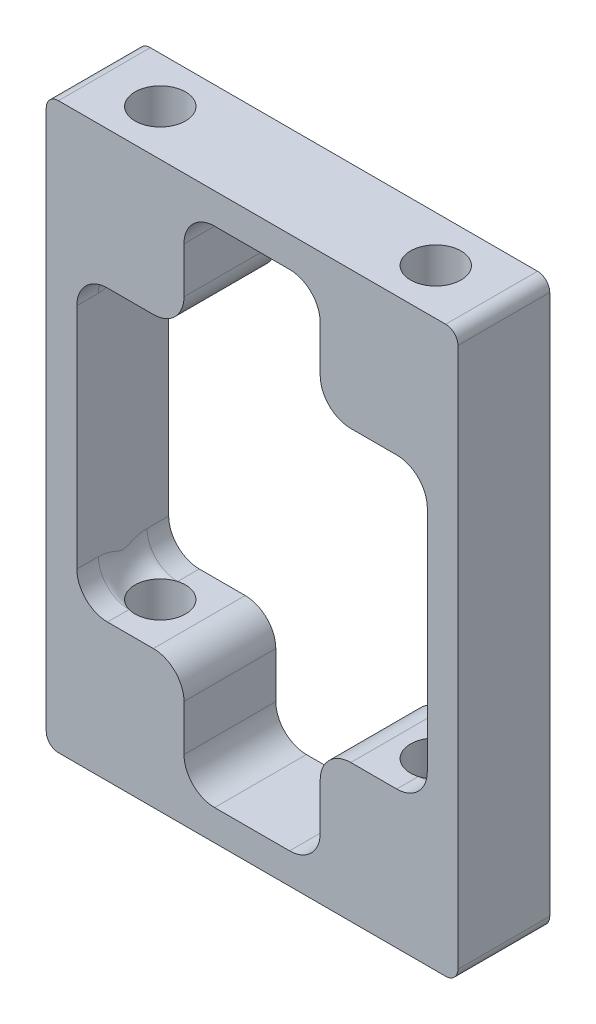
SolidWorks part; units mm, degrees
material "1060 合金"
ref_plane "前视基准面" through (0, 0, 0) normal (0, 0, 1) x (1, 0, 0)
ref_plane "上视基准面" through (0, 0, 0) normal (0, 1, 0) x (1, 0, 0)
ref_plane "右视基准面" through (0, 0, 0) normal (1, 0, 0) x (0, 0, -1)
other "Configuration Table"
sketch "草图1" plane through (0, 0, 0) normal (0, 0, 1) x (1, 0, 0)
  line L1 (-13.45, -18.45) -> (13.45, -18.45)
  line L2 (-13.45, -18.45) -> (-13.45, 18.45)
  line L3 (-13.45, 18.45) -> (13.45, 18.45)
  line L4 (13.45, -18.45) -> (13.45, 18.45)
  line L5 (-13.45, -18.45) -> (13.45, 18.45) construction
  line L6 (-13.45, 18.45) -> (13.45, -18.45) construction
  point P0 (0, 0)
  dimension "D1" = 26.9
  dimension "D2" = 36.9
extrude "凸台-拉伸1" add sketch "草图1" along normal mid plane 6
sketch "草图2" plane through (0, 18.45, 0) normal (0, 1, 0) x (1, 0, 0)
  line L0 (-9, 0) -> (9, 0) construction
  circle A0 centre (-9, 0) radius 1
  circle A1 centre (9, 0) radius 1
  point P4 (0, 0)
  dimension "D2" = 2
  dimension "D1" = 18
extrude "切除-拉伸1" cut sketch "草图2" against normal blind 10
fillet "圆角2" radius 0.8 4 edges at (13.45, -18.45, 0) (-13.45, -18.45, 0) (-13.45, 18.45, 0) (13.45, 18.45, 0)
hole_wizard "M4 螺纹孔1" positions "草图5" profile "草图6" tap size "M4" standard "GB"
sketch "草图5" plane through (0, 18.45, 0) normal (0, 1, 0) x (1, 0, 0)
  point P0 (-9, 0)
  point P3 (9, 0)
sketch "草图6" plane through (-9, 18.45, 0) normal (1, 0, 0) x (0, 0, 1)
  line L0 (0, 0) -> (0, 10.9914)
  line L1 (0, 10.9914) -> (1.65, 10)
  line L2 (1.65, 10) -> (1.65, 0)
  line L5 (1.65, 0) -> (0, 0)
  line L10 (0, 10.9914) -> (-1.65, 10) construction
  line L11 (0, -6.35) -> (0, 107.95) construction
  dimension "螺纹孔钻头直径" = 3.3
  dimension "螺纹孔钻头深度" = 10
  dimension "导头角度" = 118
cosmetic thread "孔螺蚊线1" parameters "D1"=8, "D2"=4
cosmetic thread "孔螺蚊线2" parameters "D1"=8, "D2"=4
mirror "镜向1" about plane through (0, 0, 0) normal (0, 1, 0) of "M4 螺纹孔1"
sketch "草图7" plane through (0, 0, 3) normal (0, 0, 1) x (1, 0, 0)
  line L0 (-4.45, 16.45) -> (4.45, 16.45)
  line L1 (0, 0) -> (50000, 0) construction
  line L2 (-4.45, 16.45) -> (-4.45, 9.45)
  line L3 (-4.45, 9.45) -> (-11.45, 9.45)
  line L4 (-11.45, 9.45) -> (-11.45, -9.45)
  line L5 (4.45, 16.45) -> (4.45, 9.45)
  line L6 (4.45, 9.45) -> (11.45, 9.45)
  line L7 (11.45, 9.45) -> (11.45, -9.45)
  line L8 (0, 0) -> (0, -50000) construction
  line L9 (-13.45, 17.65) -> (-13.45, -17.65) construction
  line L10 (12.65, 18.45) -> (-12.65, 18.45) construction
  line L12 (-11.45, 9.45) -> (-11.45, 0)
  line L13 (-4.45, 9.45) -> (-11.45, 9.45)
  line L14 (-4.45, 16.45) -> (-4.45, 9.45)
  line L15 (11.45, 9.45) -> (11.45, 0)
  line L16 (4.45, 9.45) -> (11.45, 9.45)
  line L17 (4.45, 16.45) -> (4.45, 9.45)
  line L18 (-4.45, 16.45) -> (-4.45, 9.45)
  line L19 (-4.45, 9.45) -> (-11.45, 9.45)
  line L20 (-11.45, 9.45) -> (-11.45, 0)
  line L21 (4.45, 16.45) -> (4.45, 9.45)
  line L22 (4.45, 9.45) -> (11.45, 9.45)
  line L23 (11.45, 9.45) -> (11.45, 0)
  line L24 (-11.45, 9.45) -> (-11.45, 0)
  line L25 (-4.45, 9.45) -> (-11.45, 9.45)
  line L26 (-4.45, 16.45) -> (-4.45, 9.45)
  line L27 (11.45, 9.45) -> (11.45, 0)
  line L28 (4.45, 9.45) -> (11.45, 9.45)
  line L29 (4.45, 16.45) -> (4.45, 9.45)
  line L30 (4.45, -9.45) -> (11.45, -9.45)
  line L31 (4.45, -16.45) -> (4.45, -9.45)
  line L32 (-4.45, -16.45) -> (4.45, -16.45)
  line L33 (-4.45, -16.45) -> (-4.45, -9.45)
  line L34 (-4.45, -9.45) -> (-11.45, -9.45)
  dimension "D1" = 2
  dimension "D2" = 9
  dimension "D3" = 9
  dimension "D4" = 2
extrude "切除-拉伸2" cut sketch "草图7" against normal mid plane 20 contours L34 L33 L32 L31 L30 L7 L6 L5 L0 L2 L3 L4 region at (0, 0, 3)
fillet "圆角3" radius 2 12 edges at (-11.45, 9.45, 0) (-4.45, 16.45, 0) (4.45, 16.45, 0) (4.45, 9.45, 0) (11.45, 9.45, 0) (11.45, -9.45, 0) (4.45, -9.45, 0) (4.45, -16.45, 0) (-4.45, -16.45, 0) (-4.45, -9.45, 0) (-11.45, -9.45, 0) (-4.45, 9.45, 0)
